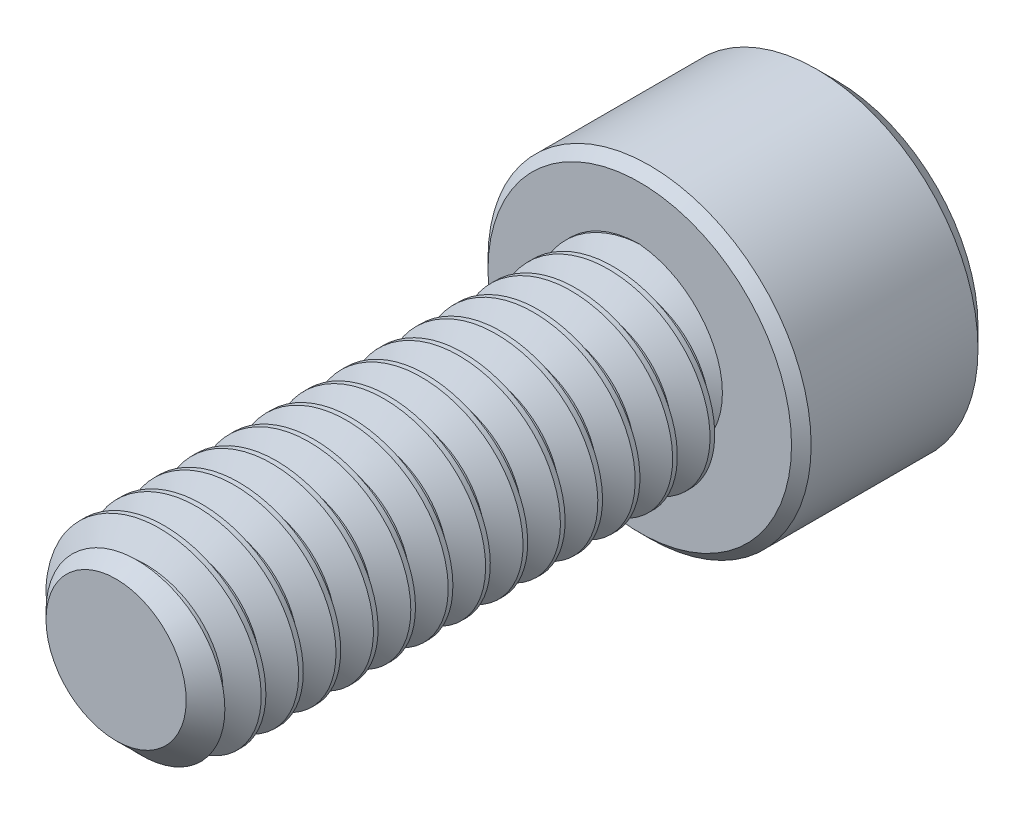
SolidWorks part; units mm, degrees
ref_plane "Front Plane" through (0, 0, 0) normal (0, 0, 1) x (1, 0, 0)
ref_plane "Top Plane" through (0, 0, 0) normal (0, 1, 0) x (1, 0, 0)
ref_plane "Right Plane" through (0, 0, 0) normal (1, 0, 0) x (0, 0, -1)
sketch "Sketch1" plane through (0, 0, 0) normal (0, 0, 1) x (1, 0, 0)
  line L0 (0, 2.0828) -> (0, -2.0828) construction
  circle A0 centre (0, 0) radius 2.0828
  dimension "OD" = 4.1656
extrude "Extrude1" add sketch "Sketch1" against normal blind 11.1125
sketch "Sketch2" plane through (0, 0, 0) normal (0, 0, 1) x (1, 0, 0)
  circle A0 centre (0, 0) radius 2.0828 construction
  circle A1 centre (0, 0) radius 2.0828
curve "Helix/Spiral1" pitch 0.7937 height 11.9062 turns 15 parameters "pitch"=0.7937
chamfer "Chamfer3" distance 0.5953 angle 45 1 edges at (2.0828, 0, 0)
sketch "Sketch3" plane through (0, 0, 0) normal (1, 0, 0) x (0, 0, -1)
  line L0 (-0.6945, 2.0828) -> (-0.3969, 1.5672)
  line L1 (-0.3969, 1.5672) -> (-0.2977, 1.5672)
  line L2 (-0.2977, 1.5672) -> (0, 2.0828)
  line L3 (-0.6945, 2.0828) -> (0, 2.0828)
  line L4 (-0.3473, 2.0828) -> (-0.3473, 1.5672) construction
  line L5 (-0.5457, 1.825) -> (-0.1488, 1.825) construction
  line L6 (0, 2.0828) -> (0, -2.0828) construction
  dimension "D1" = 0.0992
  dimension "D2" = 0.3969
  dimension "D3" = 60
sweep "Cut-Sweep1" cut profiles "Sketch3" path "Helix/Spiral1"
sketch "Sketch6" plane through (0, 0, -11.1125) normal (0, 0, -1) x (-1, 0, 0)
  circle A0 centre (0, 0) radius 3.429
  dimension "head dia" = 6.858
extrude "Extrude2" add sketch "Sketch6" along normal blind 4.1656
sketch "Sketch7" plane through (0, 0, -15.2781) normal (0, 0, -1) x (-1, 0, 0)
  line L1 (0, 2.0622) -> (-1.7859, 1.0311)
  line L2 (-1.7859, 1.0311) -> (-1.7859, -1.0311)
  line L3 (-1.7859, -1.0311) -> (0, -2.0622)
  line L4 (0, -2.0622) -> (1.7859, -1.0311)
  line L5 (1.7859, -1.0311) -> (1.7859, 1.0311)
  line L6 (1.7859, 1.0311) -> (0, 2.0622)
  circle A0 centre (0, 0) radius 1.7859 construction
  dimension "hex dia" = 3.5719
extrude "Cut-Extrude1" cut sketch "Sketch7" against normal blind 2.6789
sketch "Sketch8" plane through (0, 0, -15.2781) normal (0, 0, -1) x (-1, 0, 0)
  circle A0 centre (0, 0) radius 2.0622
extrude "Cut-Extrude2" cut sketch "Sketch8" against normal blind 0.4166 draft 45
chamfer "Chamfer1" distance 0.4166 angle 45 1 edges at (-3.429, 0, -15.2781)
chamfer "Chamfer2" distance 0.2083 angle 45 1 edges at (-3.429, 0, -11.1125)
sketch "Sketch9" plane through (0, 0, 0) normal (1, 0, 0) x (0, 0, -1)
  line L0 (0, 2.0828) -> (0, -2.0828) construction
  line L1 (4.3656, 2.0828) -> (4.3656, -2.0828) construction
  line L2 (11.1125, 3.429) -> (11.1125, -3.429) construction
  line L3 (15.2781, 3.429) -> (15.2781, -3.429) construction
  line L4 (15.2781, 0) -> (0, 0) construction
  dimension "D1" = 4.3656
  dimension "D2" = 4.1656
  dimension "D3" = 6.858
  dimension "D4" = 11.1125
equation "\"D3@Helix/Spiral1\" = \"screw length@Extrude1\"+\"pitch@Helix/Spiral1\""
equation "\"D1@Sketch3\" = \"pitch@Helix/Spiral1\"*.125"
equation "\"D2@Sketch3\" = \"pitch@Helix/Spiral1\"*.5"
equation "\"D1@Cut-Extrude1\" = \"hex dia@Sketch7\"*.75"
equation "\"D1@Chamfer1\" = \"head depth@Extrude2\"/10"
equation "\"D1@Sketch9\" = \"pitch@Helix/Spiral1\"*5.5"
equation "\"D1@Chamfer2\" = \"D1@Chamfer1\"/2"
equation "\"D1@Cut-Extrude2\" = \"D1@Chamfer2\"*2"
equation "\"D1@Chamfer3\" = \"pitch@Helix/Spiral1\"*.750"
equation "\"D2@Sketch9\" = \"head depth@Extrude2\""
equation "\"D3@Sketch9\" = \"head dia@Sketch6\""
equation "\"D4@Sketch9\" = \"screw length@Extrude1\""
